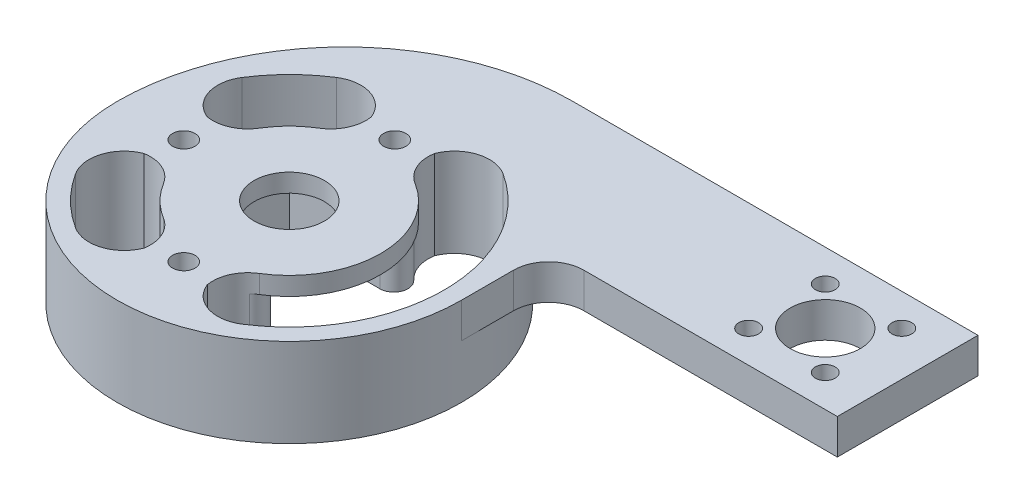
SolidWorks part; units mm, degrees
material "6061-T6 (SS)"
ref_plane "Front Plane" through (0, 0, 0) normal (0, 0, 1) x (1, 0, 0)
ref_plane "Top Plane" through (0, 0, 0) normal (0, 1, 0) x (1, 0, 0)
ref_plane "Right Plane" through (0, 0, 0) normal (1, 0, 0) x (0, 0, -1)
sketch "Sketch1" plane through (0, 0, 0) normal (0, 1, 0) x (1, 0, 0)
  line L0 (-1.1049, 0) -> (-31.0896, 0) construction
  line L1 (-1.1049, 0) -> (31.0896, 0) construction
  circle A0 centre (0, 0) radius 31.0896
  dimension "D1" = 62.1792
extrude "Boss-Extrude1" add sketch "Sketch1" along normal blind 16.002
sketch "Sketch2" plane through (0, 16.002, 0) normal (0, 1, 0) x (1, 0, 0)
  line L0 (0, 0) -> (-31.0896, 0) construction
  line L1 (0, 0) -> (31.0896, 0) construction
  line L2 (-31.0896, 0) -> (-31.0896, 41.148)
  line L3 (-31.0896, 41.148) -> (83.2104, 41.148)
  line L4 (83.2104, 41.148) -> (83.2104, 15.748)
  line L5 (31.0896, 0) -> (31.0896, 15.748)
  line L6 (31.0896, 15.748) -> (83.2104, 15.748)
  circle A0 centre (0, 0) radius 31.0896 construction
  circle A2 centre (0, 0) radius 31.0896
  arc A3 (-31.0896, 0) -> (31.0896, 0) centre (0, 0) ccw
  dimension "D1" = 0
  dimension "D2" = 114.3
  dimension "D3" = 25.4
  dimension "D4" = 15.748
extrude "Boss-Extrude2" add sketch "Sketch2" against normal blind 6.35
fillet "Fillet1" [suppressed] radius 6.35
fillet "Fillet2" radius 6.35 1 edges at (31.0896, 12.827, -15.748)
sketch "Sketch4" plane through (0, 16.002, 0) normal (0, 1, 0) x (1, 0, 0)
  line L0 (83.2104, 41.148) -> (58.166, 41.148) construction
  line L1 (83.2104, 41.148) -> (-31.0896, 41.148) construction
  line L2 (58.166, 41.148) -> (58.166, 28.448) construction
  line L3 (58.166, 28.448) -> (78.486, 28.448) construction
  line L4 (68.326, 28.448) -> (75.2408, 35.3628) construction
  line L5 (68.326, 28.448) -> (75.2408, 21.5332) construction
  line L6 (68.326, 28.448) -> (61.4112, 21.5332) construction
  line L7 (68.326, 28.448) -> (61.4112, 35.3628) construction
  circle A0 centre (61.4112, 35.3628) radius 1.778
  circle A1 centre (75.2408, 35.3628) radius 1.778
  circle A2 centre (75.2408, 21.5332) radius 1.778
  circle A3 centre (68.326, 28.448) radius 6.35
  circle A4 centre (61.4112, 21.5332) radius 1.778
extrude "Cut-Extrude2" cut sketch "Sketch4" against normal up to next
sketch "Sketch7" plane through (0, 0, 0) normal (0, 1, 0) x (1, 0, 0)
  line L0 (0, 27.94) -> (0, -31.0896)
  line L1 (0, 0) -> (-7.4507, 26.9283)
  line L2 (-7.4507, -26.9283) -> (0, 0)
  line L3 (0, 0) -> (7.4507, 26.9283)
  line L4 (0, 0) -> (7.4507, -26.9283)
  line L5 (-26.9283, 7.4507) -> (0, 0)
  line L6 (0, 0) -> (26.9283, -7.4507) construction
  line L7 (-26.9283, -7.4507) -> (0, 0)
  line L8 (0, 0) -> (26.9283, 7.4507) construction
  line L9 (0, 0) -> (-26.2234, 0) construction
  circle A0 centre (0, 0) radius 16.51
  circle A1 centre (0, 0) radius 27.94
  circle A2 centre (0, 0) radius 31.0896 construction
  circle A3 centre (-19.05, 0) radius 2.0193
  circle A4 centre (0, 19.05) radius 2.0193
  circle A5 centre (0, -19.05) radius 2.0193
  circle A6 centre (0, 0) radius 19.05 construction
  dimension "D1" = 33.02
  dimension "D2" = 55.88
  dimension "D3" = 4.0386
  dimension "D4" = 38.1
  dimension "D5" = 5.08
  dimension "D6" = 5.08
  dimension "D7" = 5.08
  dimension "D8" = 5.08
extrude "Cut-Extrude4" cut sketch "Sketch7" along normal through all contours L4 A1 L3 A0 | L7 A1 L2 A0 | L1 A1 L5 A0 | A3 | A5 | A4 region at (16.8291, 0, 0) region at (-15.3599, 0, -15.3599) region at (-15.3599, 0, 15.3599)
fillet "Fillet7" radius 6.35 12 edges at (-26.9283, 8.001, -7.4507) (-7.4507, 8.001, -26.9283) (-4.4027, 8.001, -15.9122) (4.4027, 8.001, -15.9122) (7.4507, 8.001, -26.9283) (4.4027, 8.001, 15.9122) (7.4507, 8.001, 26.9283) (-7.4507, 8.001, 26.9283) (-4.4027, 8.001, 15.9122) (-15.9122, 8.001, 4.4027) (-26.9283, 8.001, 7.4507) (-15.9122, 8.001, -4.4027)
fillet "Fillet8" radius 41.148 1 edges at (-31.0896, 12.827, -41.148)
sketch "Sketch8" plane through (0, 0, 0) normal (0, -1, 0) x (1, 0, 0)
  line L0 (-10.414, 10.414) -> (10.414, 10.414)
  line L1 (10.414, 10.414) -> (10.414, -10.414) construction
  line L2 (10.414, -10.414) -> (-10.414, -10.414)
  line L3 (-10.414, -10.414) -> (-10.414, 10.414)
  line L4 (10.414, 10.414) -> (-10.414, -10.414) construction
  line L5 (-10.414, 10.414) -> (10.414, -10.414) construction
  arc A0 (10.414, 10.414) -> (10.414, -10.414) centre (10.414, 0) cw
  dimension "D2" = 10.414
  dimension "D1" = 20.828
extrude "Cut-Extrude5" cut sketch "Sketch8" against normal blind 12.7
fillet "Fillet9" radius 2.54 2 edges at (13.0872, 6.35, 10.0651) (13.0872, 6.35, -10.0651)
sketch "Sketch9" plane through (0, 12.7, 0) normal (0, -1, 0) x (1, 0, 0)
  circle A0 centre (0, 0) radius 6.35
  dimension "D1" = 12.7
extrude "Cut-Extrude6" cut sketch "Sketch9" against normal up to surface (3.302 mm away) up to face at (0, 16.002, 21.0693)
